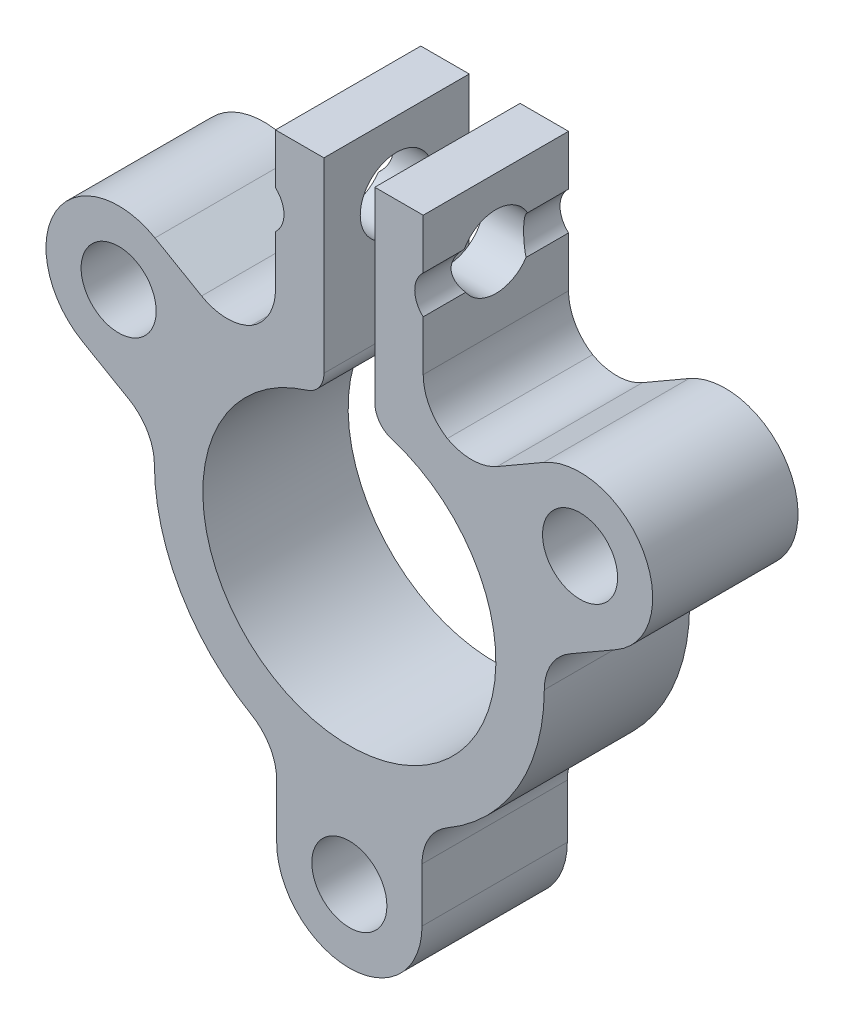
SolidWorks part; units mm, degrees
ref_plane "正面" through (0, 0, 0) normal (0, 0, 1) x (1, 0, 0)
ref_plane "平面" through (0, 0, 0) normal (0, 1, 0) x (1, 0, 0)
ref_plane "右側面" through (0, 0, 0) normal (1, 0, 0) x (0, 0, -1)
sketch "ｽｹｯﾁ1" plane through (0, 0, 0) normal (0, 0, 1) x (1, 0, 0)
  line L0 (-1.05, 5.9582) -> (-1.05, 14.4498)
  line L1 (-1.05, 14.4498) -> (-3.05, 14.4498)
  line L2 (-3.05, 14.4498) -> (-3.05, 7.4498)
  line L3 (1.05, 5.9582) -> (1.05, 14.4498)
  line L4 (1.05, 14.4498) -> (3.05, 14.4498)
  line L5 (3.05, 14.4498) -> (3.05, 7.4498)
  line L6 (0, 0) -> (0, 14.4498) construction
  line L7 (-1.05, 14.4498) -> (1.05, 14.4498) construction
  arc A0 (1.05, 5.9582) -> (-1.05, 5.9582) centre (0, 0) cw
  arc A1 (3.05, 7.4498) -> (-3.05, 7.4498) centre (0, 0) cw
  point P6 (0, 10.4178)
  point P12 (0, 14.4498)
  dimension "D1" = 6.05
  dimension "D2" = 2
  dimension "D3" = 2.1
  dimension "D4" = 2
  dimension "D5" = 7
extrude "ﾎﾞｽ - 押し出し1" add sketch "ｽｹｯﾁ1" along normal blind 6
sketch "ｽｹｯﾁ2" plane through (3.05, 0, 0) normal (1, 0, 0) x (0, 0, -1)
  line L0 (-3, 7.4498) -> (-3, 14.4498) construction
  line L1 (-6, 7.4498) -> (0, 7.4498) construction
  line L2 (-6, 14.4498) -> (0, 14.4498) construction
  circle A0 centre (-3, 11.6498) radius 1.5
  point P8 (0, 0)
  dimension "D1" = 3
  dimension "D2" = 2.8
extrude "ｶｯﾄ - 押し出し1" cut sketch "ｽｹｯﾁ2" against normal through all
sketch "ｽｹｯﾁ3" plane through (0, 0, 6) normal (0, 0, 1) x (1, 0, 0)
  line L0 (0, 0) -> (-9.5263, 5.5) construction
  line L2 (-4.9693, 6.3331) -> (-8.0263, 8.0981)
  line L3 (-6.4978, 7.2156) -> (-9.4978, 2.0195) construction
  line L4 (0, 0) -> (0, -6.05) construction
  line L5 (-11.0263, 2.9019) -> (-7.9693, 1.137)
  line L7 (8.0263, 8.0981) -> (4.9693, 6.3331)
  line L8 (7.9693, 1.137) -> (11.0263, 2.9019)
  line L9 (3, -11) -> (3, -7.4701)
  line L10 (-3, -7.4701) -> (-3, -11)
  arc A0 (-3.05, 7.4498) -> (3.05, 7.4498) centre (0, 0) ccw construction
  arc A1 (-4.9693, 6.3331) -> (-7.9693, 1.137) centre (0, 0) ccw
  arc A3 (-8.0263, 8.0981) -> (-11.0263, 2.9019) centre (-9.5263, 5.5) ccw
  circle A4 centre (-9.5263, 5.5) radius 1.55
  arc A5 (-1.05, 5.9582) -> (1.05, 5.9582) centre (0, 0) ccw construction
  arc A8 (7.9693, 1.137) -> (4.9693, 6.3331) centre (0, 0) ccw
  arc A9 (11.0263, 2.9019) -> (8.0263, 8.0981) centre (9.5263, 5.5) ccw
  circle A10 centre (9.5263, 5.5) radius 1.55
  arc A11 (-3, -7.4701) -> (3, -7.4701) centre (0, 0) ccw
  arc A12 (-3, -11) -> (3, -11) centre (0, -11) ccw
  circle A13 centre (0, -11) radius 1.55
  point P14 (-7.9978, 4.6175)
  dimension "D1" = 3.1
  dimension "D2" = 3
  dimension "D3" = 120
  dimension "D4" = 11
  dimension "D5" = 3
extrude "ﾎﾞｽ - 押し出し2" add sketch "ｽｹｯﾁ3" against normal through all
fillet "ﾌｨﾚｯﾄ1" radius 2.1 8 edges at (3.05, 7.4498, 3) (-7.9693, 1.137, 3) (-4.9693, 6.3331, 3) (-3.05, 7.4498, 3) (-3, -7.4701, 3) (3, -7.4701, 3) (7.9693, 1.137, 3) (4.9693, 6.3331, 3)
fillet "ﾌｨﾚｯﾄ2" radius 1 2 edges at (1.05, 5.9582, 3) (-1.05, 5.9582, 3)
sketch "ｽｹｯﾁ4" plane through (0, 0, 6) normal (0, 0, 1) x (1, 0, 0)
  line L0 (-3.05, 11.5981) -> (3.05, 11.5981) construction
  line L1 (-3.05, 14.4498) -> (-3.05, 8.7464) construction
  line L2 (3.05, 8.7464) -> (3.05, 14.4498) construction
  line L3 (3.75, 11.5981) -> (3.05, 11.5981) construction
  line L4 (0, 14.5061) -> (0, 0) construction
  circle A0 centre (3.75, 11.5981) radius 1.05
  circle A1 centre (-3.75, 11.5981) radius 1.05
  point P11 (0, 0)
  dimension "D1" = 0.7
  dimension "D2" = 2.1
extrude "ｶｯﾄ - 押し出し2" cut sketch "ｽｹｯﾁ4" against normal through all
